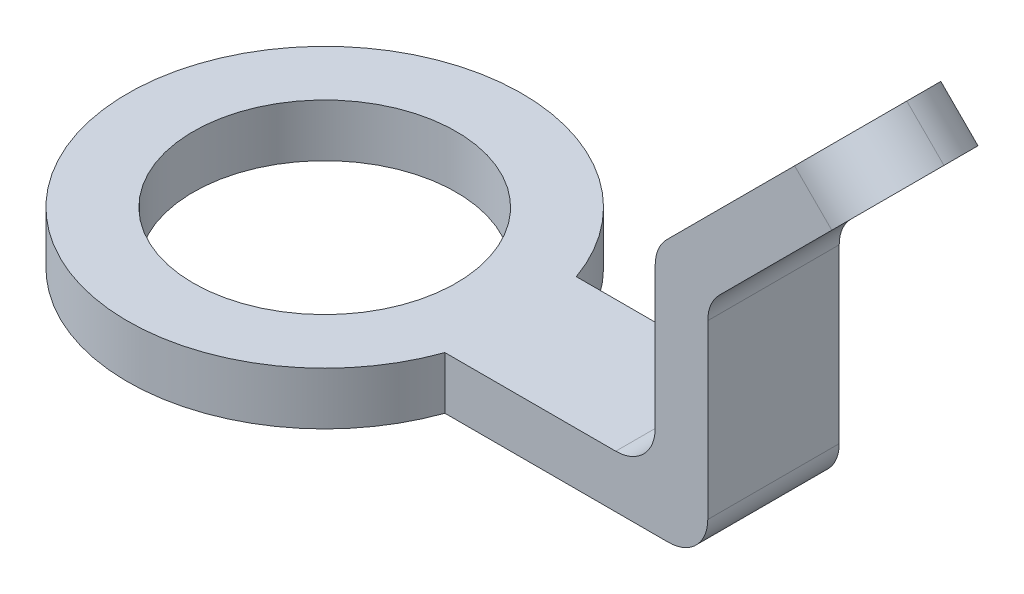
SolidWorks part; units mm, degrees
ref_plane "Front Plane" through (0, 0, 0) normal (0, 0, 1) x (1, 0, 0)
ref_plane "Top Plane" through (0, 0, 0) normal (0, 1, 0) x (1, 0, 0)
ref_plane "Right Plane" through (0, 0, 0) normal (1, 0, 0) x (0, 0, -1)
sketch "Sketch2" plane through (0, 0, 0) normal (0, 1, 0) x (1, 0, 0)
  line L0 (0, 0) -> (34.1421, 0) construction
  line L1 (34.1421, 5) -> (34.1421, -5)
  line L2 (34.1421, -5) -> (14.1421, -5)
  line L3 (34.1421, 5) -> (14.1421, 5)
  arc A0 (14.1421, 5) -> (14.1421, -5) centre (0, 0) ccw
  circle A1 centre (0, 0) radius 10
  dimension "D1" = 30
  dimension "D5" = 20
  dimension "D2" = 5
  dimension "D3" = 5
  dimension "D4" = 20
extrude "Boss-Extrude1" add sketch "Sketch2" along normal blind 4
sketch "Sketch3" plane through (0, 0, 5) normal (0, 0, 1) x (1, 0, 0)
  line L0 (34.1421, 4) -> (34.1421, 17.3431)
  line L1 (34.1421, 17.3431) -> (47.1127, 30.3137)
  line L2 (47.1127, 30.3137) -> (44.2843, 33.1421)
  line L3 (44.2843, 33.1421) -> (30.1421, 19)
  line L4 (30.1421, 19) -> (30.1421, 4)
  line L5 (14.1421, 4) -> (34.1421, 4) construction
  line L6 (30.1421, 4) -> (34.1421, 4)
  dimension "D1" = 4
  dimension "D2" = 4
  dimension "D3" = 135
  dimension "D4" = 15
  dimension "D5" = 20
extrude "Boss-Extrude2" add sketch "Sketch3" against normal blind 10
sketch "Sketch4" plane through (0, 0, 0) normal (0, -1, 0) x (1, 0, 0)
  circle A0 centre (0, 0) radius 12
  circle A1 centre (0, 0) radius 13
  dimension "D1" = 24
  dimension "D2" = 26
extrude "Boss-Extrude3" [suppressed] add sketch "Sketch4" along normal blind 1
fillet "Fillet1" radius 5 2 edges at (45.6985, 31.7279, -5) (45.6985, 31.7279, 5)
sketch "Sketch5" plane through (5.5711, -5.5711, 0) normal (-0.7071, 0.7071, 0) x (0.7071, 0.7071, 0)
  circle A0 centre (49.7487, 0) radius 2.5
  dimension "D1" = 5
hole_wizard "M3 Clearance Hole1" positions "Sketch6" profile "Sketch7" hole size "M3" standard "ANSI Metric" end condition through all
sketch "Sketch6" plane through (5.5711, -5.5711, 0) normal (-0.7071, 0.7071, 0) x (0.7071, 0.7071, 0)
  point P0 (49.7487, 0)
sketch "Sketch7" plane through (40.7487, 29.6066, 0) normal (0, 0, 1) x (-0.7071, -0.7071, 0)
  line L0 (0, 0) -> (0, 25.435)
  line L1 (0, 25.435) -> (1.8, 25.435)
  line L2 (1.8, 25.435) -> (1.8, 0)
  line L5 (1.8, 0) -> (0, 0)
  line L11 (0, -6.35) -> (0, 107.95) construction
  dimension "Thru Hole Dia." = 3.6
  dimension "Thru Hole Depth" = 25.435
fillet "Fillet2" radius 3 4 edges at (34.1421, 17.3431, 0) (30.1421, 19, 0) (34.1421, 0, 0) (30.1421, 4, 0)
